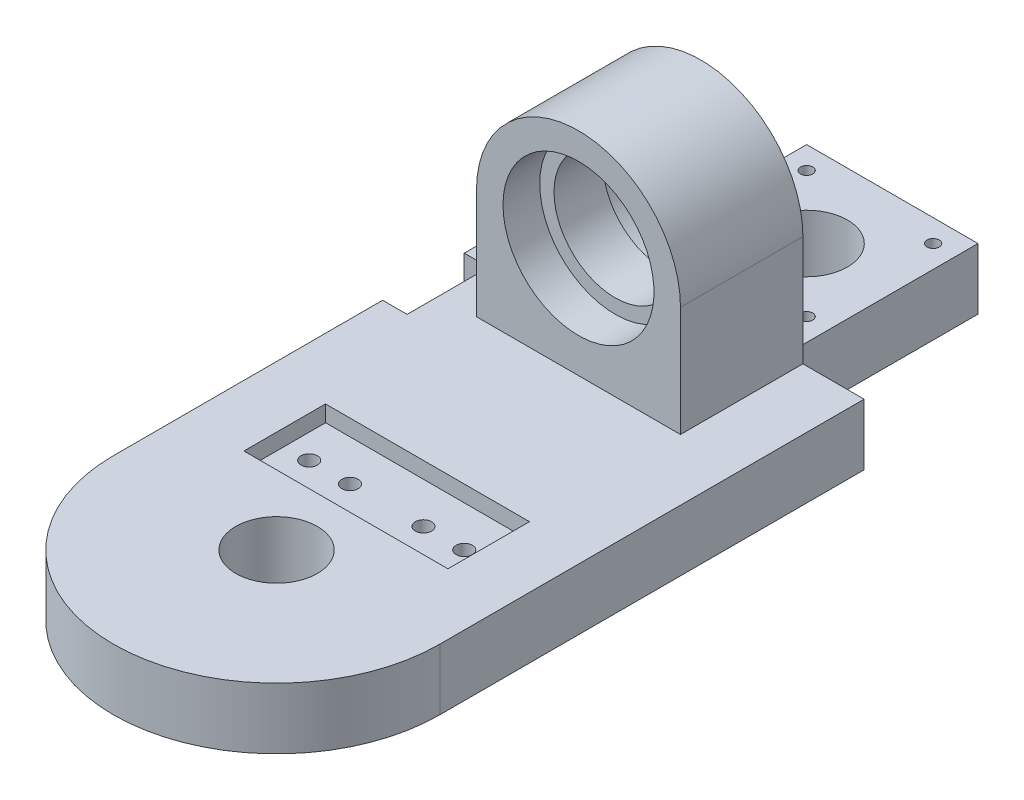
SolidWorks part; units mm, degrees
ref_plane "Ebene vorne" through (0, 0, 0) normal (0, 0, 1) x (1, 0, 0)
ref_plane "Ebene oben" through (0, 0, 0) normal (0, 1, 0) x (1, 0, 0)
ref_plane "Ebene rechts" through (0, 0, 0) normal (1, 0, 0) x (0, 0, -1)
sketch "Skizze1" plane through (0, 0, 0) normal (0, 1, 0) x (1, 0, 0)
  line L0 (-25.9794, -40) -> (25.9794, -40) construction
  line L1 (-40, 0) -> (40, 0)
  line L2 (-40, 0) -> (-40, 104)
  line L4 (40, 0) -> (40, 104)
  line L5 (-40, 0) -> (40, 104) construction
  line L6 (-40, 104) -> (40, 0) construction
  line L9 (-40, 104) -> (-40, 78)
  line L12 (-40, 104) -> (40, 104)
  line L13 (-21.0848, 151) -> (20.9152, 109) construction
  line L21 (-21.0848, 104) -> (20.9152, 104)
  line L22 (-21.0848, 104) -> (-21.0848, 151)
  line L23 (-21.0848, 151) -> (20.9152, 151)
  line L24 (20.9152, 104) -> (20.9152, 151)
  line L25 (20.9152, 151) -> (-21.0848, 109) construction
  circle A0 centre (0, 0) radius 40
  circle A2 centre (-0.0848, 130) radius 10
  circle A3 centre (-15.5848, 145.5) radius 1.5
  circle A4 centre (15.4152, 145.5) radius 1.5
  circle A5 centre (15.4152, 114.5) radius 1.5
  circle A6 centre (-15.5848, 114.5) radius 1.5
  point P7 (0, 52)
  point P11 (0, -40)
  point P31 (-0.0848, 130)
  dimension "D1" = 80
  dimension "D5" = 144
  dimension "D4" = 42
  dimension "D6" = 4
  dimension "D2" = 42
  dimension "D3" = 5
extrude "Aufsatz-Linear austragen1" add sketch "Skizze1" along normal blind 15
sketch "Skizze2" plane through (0, 15, 0) normal (0, 1, 0) x (1, 0, 0)
  line L0 (-40, 104) -> (-21.0848, 104) construction
  line L1 (25, 104) -> (-25, 104)
  line L2 (25, 104) -> (25, 74)
  line L3 (25, 74) -> (-25, 74)
  line L4 (-25, 104) -> (-25, 74)
  line L5 (25, 104) -> (-25, 74) construction
  line L6 (25, 74) -> (-25, 104) construction
  point P4 (0, 89)
  dimension "D1" = 50
  dimension "D2" = 30
extrude "Aufsatz-Linear austragen2" add sketch "Skizze2" along normal blind 52
sketch "Skizze3" plane through (0, 0, -104) normal (0, 0, -1) x (-1, 0, 0)
  line L0 (-25, 67) -> (25, 67) construction
  line L5 (-25, 67) -> (25, 67)
  line L8 (25, 67) -> (25, 17)
  line L9 (-25, 67) -> (25, 17) construction
  line L10 (-25, 17) -> (25, 67) construction
  line L12 (-25, 42) -> (-25, 67)
  line L13 (25, 67) -> (-25, 67)
  line L14 (-25, 67) -> (-25, 15) construction
  line L15 (25, 67) -> (25, 42)
  line L16 (-25, 67) -> (-25, 17)
  line L17 (25, 67) -> (25, 15) construction
  line L18 (40, 15) -> (25, 15) construction
  circle A1 centre (0, 42) radius 15
  circle A2 centre (0, 42) radius 25
  point P4 (0, 42)
  line M10 (25, 67) -> (-25, 67)
  line M15 (-25, 67) -> (-25, 15)
  dimension "D1" = 2
extrude "Schnitt-Linear austragen9" cut sketch "Skizze3" against normal blind 30 contours A1 | A2 L13 M15 | A2 L8 M10 region at (19.4158, 61.4158, -104) region at (-19.4158, 61.4158, -104) region at (0, 42, -104)
sketch "Skizze4" plane through (0, 0, -104) normal (0, 0, -1) x (-1, 0, 0)
  line L9 (25, 42) -> (25, 15) construction
  line L10 (-25, 17) -> (25, 17)
  line L11 (-25, 17) -> (-25, 67)
  line L12 (25, 42) -> (25, 15) construction
  line L14 (-25, 17) -> (25, 17)
  line L17 (40, 15) -> (25, 15) construction
  line L18 (-25, 67) -> (25, 67)
  line L19 (25, 17) -> (25, 67)
  line L20 (-25, 42) -> (-25, 15) construction
  line L21 (-25, 67) -> (25, 17) construction
  line L22 (25, 67) -> (-25, 17) construction
  arc A3 (25, 42) -> (-25, 42) centre (0, 42) ccw construction
  circle A4 centre (0, 42) radius 18.5
  dimension "D1" = 37
  dimension "D2" = 2
  dimension "D3" = 50
extrude "Schnitt-Linear austragen10" cut sketch "Skizze4" against normal blind 9 contours A4
ref_plane "Ebene1" through (0, 0, -89) normal (0, 0, -1) x (-1, 0, 0)
sketch "Skizze5" plane through (0, 15, 0) normal (0, 1, 0) x (1, 0, 0)
  line L0 (40, 0) -> (40, 104) construction
  line L1 (-25, 74) -> (40, 74)
  line L2 (-25, 74) -> (-25, 37)
  line L3 (-25, 37) -> (40, 37)
  line L4 (40, 74) -> (40, 37)
  line L5 (-25, 74) -> (40, 37) construction
  line L6 (-25, 37) -> (40, 74) construction
  line L7 (0, 0) -> (0, 27) construction
  line L8 (-25, 37) -> (40, 37)
  line L14 (-25, 17) -> (25, 17)
  line L15 (-25, 17) -> (-25, 37)
  line L16 (-25, 37) -> (25, 37)
  line L17 (25, 17) -> (25, 37)
  line L18 (-25, 17) -> (25, 37) construction
  line L19 (-25, 37) -> (25, 17) construction
  point P4 (7.5, 55.5)
  point P13 (0, 27)
  dimension "D1" = 20
  dimension "D2" = 37
  dimension "D3" = 50
extrude "Schnitt-Linear austragen3" cut sketch "Skizze5" against normal blind 4 contours L14 L17 L3 L16 L15 region at (0, 15, -27)
sketch "Skizze6" plane through (0, 11, 0) normal (0, 1, 0) x (1, 0, 0)
  line L0 (-25, 27) -> (25, 27) construction
  line L3 (0, 27) -> (0, 3.2798) construction
  line L5 (25, 17) -> (25, 37) construction
  circle A0 centre (9, 27) radius 2
  circle A1 centre (-9, 27) radius 2
  circle A2 centre (19, 27) radius 2
  circle A3 centre (-19, 27) radius 2
  dimension "D2" = 4
  dimension "D3" = 4
  dimension "D4" = 10
extrude "Schnitt-Linear austragen4" cut sketch "Skizze6" against normal blind 11
sketch "Skizze8" plane through (0, 0, 0) normal (0, -1, 0) x (1, 0, 0)
  circle A0 centre (0, 0) radius 20
  circle A1 centre (0, 0) radius 32.5
  circle A2 centre (0, 0) radius 26.25
  dimension "D1" = 40
  dimension "D2" = 65
  dimension "D3" = 52.5
extrude "Schnitt-Linear austragen5" cut sketch "Skizze8" against normal blind 4 contours A1 A2 region at (-31.5808, 0, 0)
sketch "Skizze10" plane through (0, 0, 0) normal (0, -1, 0) x (1, 0, 0)
  circle A0 centre (0, 0) radius 10
sketch "Skizze11" plane through (0, 0, 0) normal (0, -1, 0) x (1, 0, 0)
  circle A0 centre (9, -27) radius 3.5
  circle A1 centre (19, -27) radius 3.5
  circle A2 centre (-19, -27) radius 3.5
  circle A3 centre (-9, -27) radius 3.5
  dimension "D1" = 7
  dimension "D2" = 7
extrude "Schnitt-Linear austragen6" cut sketch "Skizze11" against normal offset from surface (8 mm away) 8 up to face at (0, 0, -14.3178)
mirror "Spiegeln2" about plane through (0, 0, -89) normal (0, 0, -1) of "Schnitt-Linear austragen10"
ref_plane "Plane1" through (25, 15, -74) normal (1, 0, 0) x (0, 0, -1)
sketch "Skizze14" plane through (0, 15, 0) normal (0, 1, 0) x (1, 0, 0)
  line L0 (-40, 104) -> (-40, 86) construction
  line L1 (-40, 0) -> (-40, 104) construction
  line L2 (-40, 104) -> (-25, 104) construction
  line L4 (-40, 86) -> (-34, 86)
  line L5 (-40, 86) -> (-40, 66)
  line L6 (-40, 66) -> (-34, 66)
  line L7 (-34, 86) -> (-34, 66)
  line L8 (-40, 86) -> (-34, 66) construction
  line L9 (-40, 66) -> (-34, 86) construction
  point P9 (-37, 76)
  dimension "D1" = 20
  dimension "D2" = 18
  dimension "D3" = 6
extrude "Schnitt-Linear austragen11" cut sketch "Skizze14" against normal blind 15 contours L5 L4 L7 L6
sketch "Skizze15" plane through (-34, 0, 0) normal (-1, 0, 0) x (0, 0, 1)
  circle A1 centre (-80.5, 7.5) radius 1.25
  circle A2 centre (-71, 7.5) radius 1.25
  circle A3 centre (-71, 7.5) radius 1.25 construction
  circle A4 centre (-80.5, 7.5) radius 1.25 construction
extrude "Schnitt-Linear austragen12" cut sketch "Skizze15" against normal blind 6
extrude "Cut-Extrude1" cut sketch "Skizze10" against normal blind 15
